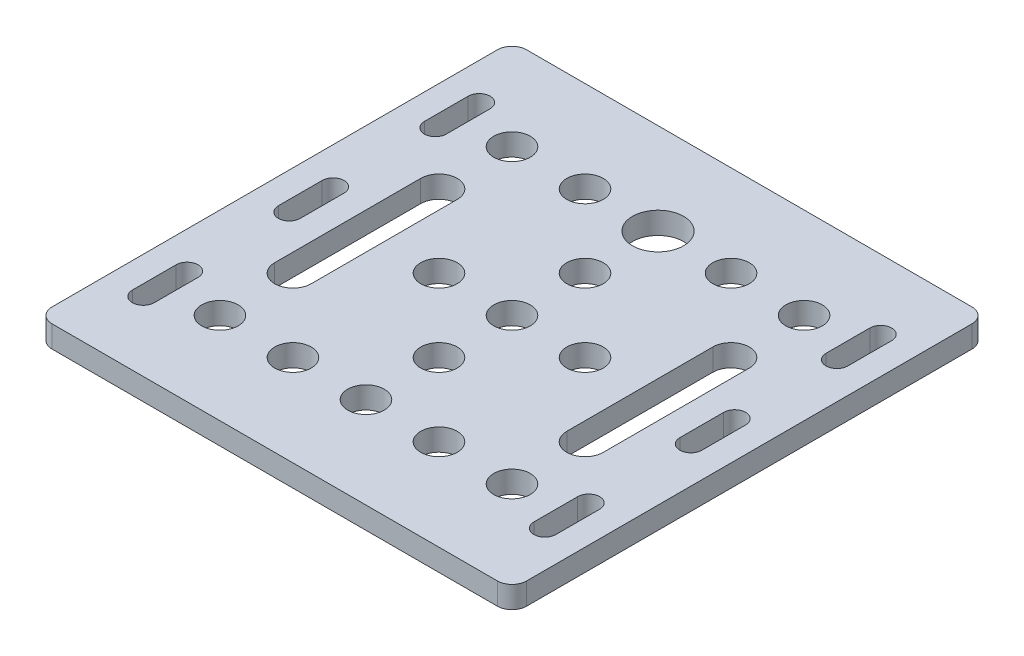
SolidWorks part; units mm, degrees
ref_plane "Front" through (0, 0, 0) normal (0, 0, 1) x (1, 0, 0)
ref_plane "Top" through (0, 0, 0) normal (0, 1, 0) x (1, 0, 0)
ref_plane "Right" through (0, 0, 0) normal (1, 0, 0) x (0, 0, -1)
sketch "Sketch1" plane through (0, 0, 0) normal (0, 1, 0) x (1, 0, 0)
  line L1 (-32.5, 32.5) -> (32.5, 32.5)
  line L2 (-32.5, 32.5) -> (-32.5, -32.5)
  line L3 (-32.5, -32.5) -> (32.5, -32.5)
  line L4 (32.5, 32.5) -> (32.5, -32.5)
  line L5 (-32.5, 32.5) -> (32.5, -32.5) construction
  line L6 (-32.5, -32.5) -> (32.5, 32.5) construction
  point P0 (0, 0)
  dimension "D1" = 65
extrude "Boss-Extrude1" add sketch "Sketch1" along normal mid plane 3
sketch "Sketch2" plane through (0, 0, 0) normal (0, 1, 0) x (1, 0, 0)
  circle A0 centre (0, 0) radius 2.5
  circle A1 centre (0, 10) radius 2.5
  circle A3 centre (0, 0) radius 2.5
  circle A4 centre (0, 10) radius 2.5
  circle A5 centre (0, -10) radius 2.5
  circle A6 centre (0, 0) radius 2.5
  circle A7 centre (0, -10) radius 2.5
  circle A8 centre (0, -20) radius 2.5
  circle A9 centre (-10, 0) radius 2.5
  circle A10 centre (-10, 20) radius 2.5
  circle A13 centre (-10, -20) radius 2.5
  circle A15 centre (-20, 20) radius 2.5
  circle A18 centre (-20, -20) radius 2.5
  circle A19 centre (0, 0) radius 2.5
  circle A21 centre (0, 10) radius 2.5
  circle A22 centre (0, -10) radius 2.5
  circle A23 centre (0, -20) radius 2.5
  circle A24 centre (-10, 0) radius 2.5
  circle A25 centre (-10, 20) radius 2.5
  circle A28 centre (-10, -20) radius 2.5
  circle A29 centre (10, 0) radius 2.5
  circle A30 centre (10, 20) radius 2.5
  circle A33 centre (10, -20) radius 2.5
  circle A34 centre (0, 0) radius 2.5
  circle A36 centre (0, 10) radius 2.5
  circle A37 centre (0, -10) radius 2.5
  circle A38 centre (0, -20) radius 2.5
  circle A39 centre (10, 0) radius 2.5
  circle A40 centre (10, 20) radius 2.5
  circle A43 centre (10, -20) radius 2.5
  circle A45 centre (20, 20) radius 2.5
  circle A48 centre (20, -20) radius 2.5
  circle A49 centre (20, 10) radius 2.5 [skipped]
  circle A50 centre (10, 10) radius 2.5 [skipped]
  circle A51 centre (-10, 10) radius 2.5 [skipped]
  circle A52 centre (-20, 10) radius 2.5 [skipped]
  circle A53 centre (-10, 10) radius 2.5 [skipped]
  circle A54 centre (10, 10) radius 2.5 [skipped]
  circle A55 centre (20, 0) radius 2.5 [skipped]
  circle A56 centre (10, -10) radius 2.5 [skipped]
  circle A57 centre (10, -10) radius 2.5 [skipped]
  circle A58 centre (20, -10) radius 2.5 [skipped]
  circle A59 centre (-10, -10) radius 2.5 [skipped]
  circle A60 centre (-20, -10) radius 2.5 [skipped]
  circle A61 centre (-10, -10) radius 2.5 [skipped]
  circle A62 centre (-20, 0) radius 2.5 [skipped]
  circle A63 centre (0, 20) radius 2.5 [skipped]
  point P4 (0, 0)
  dimension "D1" = 5
  dimension "D2" = 3
  dimension "D3" = 3
  dimension "D4" = 3
  dimension "D5" = 3
extrude "Cut-Extrude1" cut sketch "Sketch2" against normal through all both and the other way through all contours A10 | A15 | A30 | A45 | A1 | A9 | A0 | A29 | A5 | A18 | A13 | A8 | A33 | A48 region at (0, 0, 0) region at (0, 0, -10) region at (0, 0, 10) region at (0, 0, 20) region at (-10, 0, 0) region at (-10, 0, -20) region at (-10, 0, 20) region at (-20, 0, -20) region at (-20, 0, 20) region at (10, 0, 0) region at (10, 0, -20) region at (10, 0, 20) region at (20, 0, -20) region at (20, 0, 20)
sketch "Sketch3" plane through (0, 0, 0) normal (0, 1, 0) x (1, 0, 0)
  line L0 (20, 10) -> (20, -10) construction
  line L1 (22.5, 10) -> (22.5, -10)
  line L2 (17.5, 10) -> (17.5, -10)
  line L3 (0, -50) -> (0, 50) construction
  line L4 (-20, 10) -> (-20, -10) construction
  line L5 (-22.5, 10) -> (-22.5, -10)
  line L6 (-17.5, 10) -> (-17.5, -10)
  arc A0 (22.5, 10) -> (17.5, 10) centre (20, 10) ccw
  arc A1 (17.5, -10) -> (22.5, -10) centre (20, -10) ccw
  arc A2 (-22.5, 10) -> (-17.5, 10) centre (-20, 10) cw
  arc A3 (-17.5, -10) -> (-22.5, -10) centre (-20, -10) cw
  point P3 (20, 0)
  point P8 (0, 0)
  point P14 (-20, 0)
  dimension "D1" = 5
  dimension "D2" = 20
extrude "Cut-Extrude2" cut sketch "Sketch3" against normal through all both and the other way through all
sketch "Sketch4" plane through (0, 0, 0) normal (0, 1, 0) x (1, 0, 0)
  circle A0 centre (0, 20) radius 3.5
  point P2 (0, 0)
  dimension "D1" = 7
  dimension "D2" = 20
extrude "Cut-Extrude3" cut sketch "Sketch4" against normal through all both and the other way through all
sketch "Sketch5" plane through (0, 0, 0) normal (0, 1, 0) x (1, 0, 0)
  line L0 (27.5, 3) -> (27.5, -3) construction
  line L1 (29, 3) -> (29, -3)
  line L2 (26, 3) -> (26, -3)
  line L3 (27.5, 23) -> (27.5, 17) construction
  line L4 (29, 23) -> (29, 17)
  line L5 (26, 23) -> (26, 17)
  line L6 (27.5, 3) -> (27.5, -3) construction
  line L7 (29, 3) -> (29, -3)
  line L8 (26, 3) -> (26, -3)
  line L9 (27.5, -17) -> (27.5, -23) construction
  line L10 (29, -17) -> (29, -23)
  line L11 (26, -17) -> (26, -23)
  line L13 (0, -50) -> (0, 50) construction
  line L14 (-27.5, -17) -> (-27.5, -23) construction
  line L15 (-29, -17) -> (-29, -23)
  line L16 (-26, -17) -> (-26, -23)
  line L17 (-27.5, 23) -> (-27.5, 17) construction
  line L18 (-29, 23) -> (-29, 17)
  line L19 (-26, 23) -> (-26, 17)
  line L20 (-27.5, 3) -> (-27.5, -3) construction
  line L21 (-29, 3) -> (-29, -3)
  line L22 (-26, 3) -> (-26, -3)
  arc A0 (29, 3) -> (26, 3) centre (27.5, 3) ccw
  arc A1 (26, -3) -> (29, -3) centre (27.5, -3) ccw
  arc A2 (29, 23) -> (26, 23) centre (27.5, 23) ccw
  arc A3 (26, 17) -> (29, 17) centre (27.5, 17) ccw
  arc A4 (29, 3) -> (26, 3) centre (27.5, 3) ccw
  arc A5 (26, -3) -> (29, -3) centre (27.5, -3) ccw
  arc A6 (29, -17) -> (26, -17) centre (27.5, -17) ccw
  arc A7 (26, -23) -> (29, -23) centre (27.5, -23) ccw
  arc A8 (-29, -17) -> (-26, -17) centre (-27.5, -17) cw
  arc A9 (-26, -23) -> (-29, -23) centre (-27.5, -23) cw
  arc A10 (-29, 23) -> (-26, 23) centre (-27.5, 23) cw
  arc A11 (-26, 17) -> (-29, 17) centre (-27.5, 17) cw
  arc A12 (-29, 3) -> (-26, 3) centre (-27.5, 3) cw
  arc A13 (-26, -3) -> (-29, -3) centre (-27.5, -3) cw
  point P2 (27.5, 0)
  point P12 (27.5, 20)
  point P19 (27.5, 0)
  point P26 (27.5, -20)
  point P35 (-27.5, -20)
  point P42 (-27.5, 20)
  point P49 (-27.5, 0)
  dimension "D1" = 3
  dimension "D2" = 6
  dimension "D3" = 27.5
  dimension "D4" = 2
  dimension "D5" = 2
extrude "Cut-Extrude4" cut sketch "Sketch5" against normal through all both and the other way through all contours A9 L16 A8 L15 | L2 A1 L1 A0 | L5 A3 L4 A2 | L19 A11 L18 A10 | L22 A13 L21 A12 | L10 A7 L11 A6 region at (27.5, 0, 0) region at (27.5, 0, -20) region at (-27.5, 0, 20)
fillet "Fillet1" radius 2 4 edges at (-32.5, 0, 32.5) (32.5, 0, 32.5) (32.5, 0, -32.5) (-32.5, 0, -32.5)
